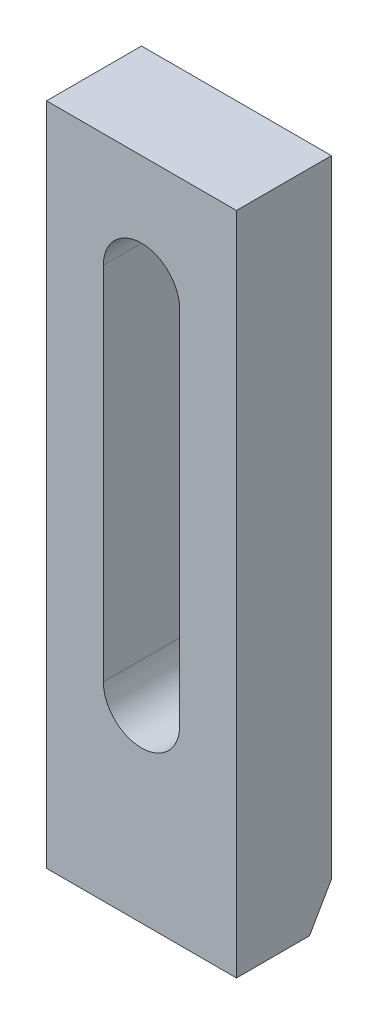
SolidWorks part; units mm, degrees
ref_plane "Спереди" through (0, 0, 0) normal (0, 0, 1) x (1, 0, 0)
ref_plane "Сверху" through (0, 0, 0) normal (0, 1, 0) x (1, 0, 0)
ref_plane "Справа" through (0, 0, 0) normal (1, 0, 0) x (0, 0, -1)
sketch "Эскиз1" plane through (0, 0, 0) normal (0, 0, 1) x (1, 0, 0)
  line L1 (0, 0) -> (50, 0)
  line L2 (0, 0) -> (0, 175)
  line L3 (0, 175) -> (50, 175)
  line L4 (50, 0) -> (50, 175)
  dimension "D1" = 50
  dimension "D2" = 175
extrude "Бобышка-Вытянуть1" add sketch "Эскиз1" along normal blind 25
sketch "Эскиз2" plane through (0, 0, 25) normal (0, 0, 1) x (1, 0, 0)
  line L1 (14.95, 50) -> (14.95, 145)
  line L2 (35.05, 50) -> (35.05, 145)
  line L3 (0, 175) -> (0, 0) construction
  line L4 (0, 0) -> (50, 0) construction
  arc A0 (14.95, 50) -> (35.05, 50) centre (25, 50) ccw
  arc A1 (14.95, 145) -> (35.05, 145) centre (25, 145) cw
  point P3 (0, 0)
  point P7 (14.95, 97.5)
  point P10 (35.05, 97.5)
  dimension "D1" = 25
  dimension "D2" = 50
extrude "Вырез-Вытянуть1" cut sketch "Эскиз2" against normal through all
chamfer "Фаска1" distance 10 angle 30 1 edges at (25, 0, 0) first distance on face at (25, 97.5, 0)
